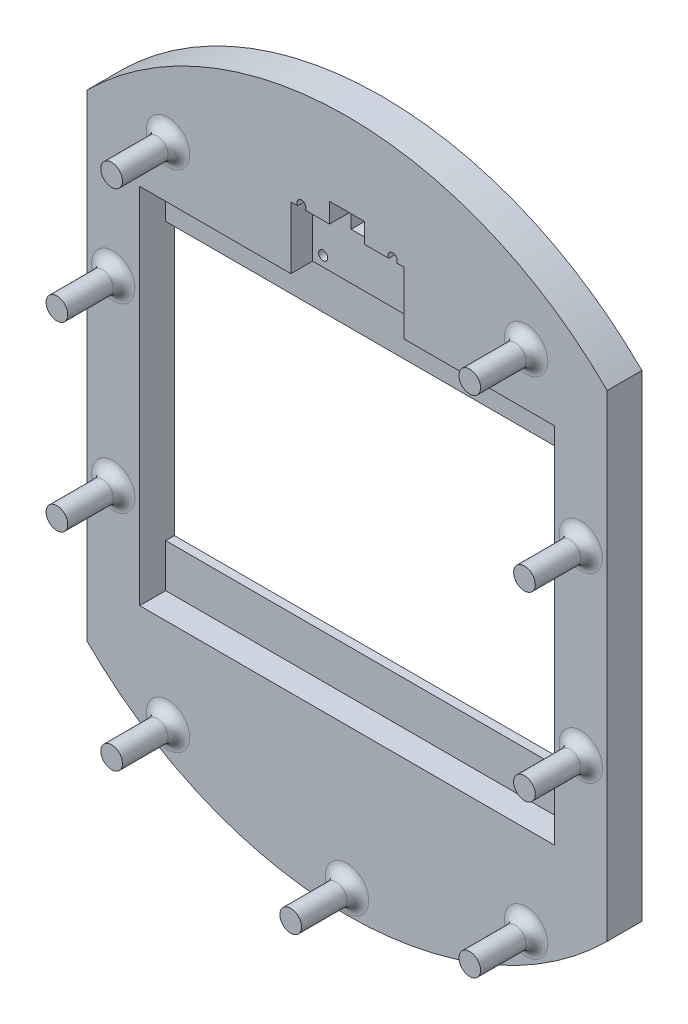
SolidWorks part; units mm, degrees
material "ABS"
ref_plane "Plano frontal" through (0, 0, 0) normal (0, 0, 1) x (1, 0, 0)
ref_plane "Plano superior" through (0, 0, 0) normal (0, 1, 0) x (1, 0, 0)
ref_plane "Plano direito" through (0, 0, 0) normal (1, 0, 0) x (0, 0, -1)
sketch "Esboço1" plane through (0, 0, 0) normal (0, 0, 1) x (1, 0, 0)
  line L0 (0, 0) -> (0, -110)
  line L1 (120, -110) -> (120, 0)
  line L2 (60, -12.6598) -> (60, -97.3402) construction
  line L3 (120, -55) -> (-37.4329, -55) construction
  line L4 (12.1875, -86.875) -> (107.8125, -86.875)
  line L5 (12.1875, -86.875) -> (12.1875, -23.125)
  line L6 (12.1875, -23.125) -> (107.8125, -23.125)
  line L7 (107.8125, -86.875) -> (107.8125, -23.125)
  line L8 (12.1875, -86.875) -> (107.8125, -23.125) construction
  line L9 (12.1875, -23.125) -> (107.8125, -86.875) construction
  arc A4 (0, 0) -> (120, 0) centre (60, -60.208) cw
  arc A5 (0, -110) -> (120, -110) centre (60, -49.792) ccw
  point P9 (60, -55)
  point P16 (0, 0)
  point P17 (60, 24.792)
  point P18 (0, 0)
  point P19 (0, 0)
  dimension "D1" = 110
  dimension "D5" = 85
  dimension "D2" = 63.75
  dimension "D3" = 95.625
extrude "Ressalto-extrusão1" add sketch "Esboço1" along normal blind 8
sketch "Esboço2" plane through (0, 0, 8) normal (0, 0, 1) x (1, 0, 0)
  line L0 (12.1875, -55) -> (107.8125, -55) construction
  line L1 (12.1875, -23.125) -> (12.1875, -86.875) construction
  line L2 (107.8125, -86.875) -> (107.8125, -23.125) construction
  line L3 (107.8125, -23.125) -> (12.1875, -23.125) construction
  line L4 (12.1875, -96.875) -> (107.8125, -96.875)
  line L5 (12.1875, -96.875) -> (12.1875, -13.125)
  line L6 (12.1875, -13.125) -> (107.8125, -13.125)
  line L7 (107.8125, -96.875) -> (107.8125, -13.125)
  line L8 (12.1875, -96.875) -> (107.8125, -13.125) construction
  line L9 (12.1875, -13.125) -> (107.8125, -96.875) construction
  point P6 (60, -55)
  dimension "D1" = 10
extrude "Corte-extrusão1" cut sketch "Esboço2" against normal blind 6
sketch "Esboço3" plane through (0, 0, 8) normal (0, 0, 1) x (1, 0, 0)
  line L0 (-24.8022, -52.3385) -> (153.0643, -52.3385) construction
  line L1 (113.9062, -94.6477) -> (113.9062, -101.6218) construction
  line L3 (60, 24.792) -> (60, -134.792) construction
  line L4 (12.1875, -13.125) -> (0, -13.125) construction
  line L5 (0, 0) -> (0, -110) construction
  line L6 (0, -13.125) -> (6.0938, -13.125) construction
  line L7 (6.0938, -13.125) -> (6.0938, -107.383) construction
  line L8 (35.13, -13.125) -> (35.13, -106.875) construction
  line L9 (107.8125, -13.125) -> (12.1875, -13.125) construction
  line L10 (60, -134.792) -> (60, -106.875)
  arc A0 (6.0938, -107.383) -> (113.9062, -107.383) centre (60, -52.3385) ccw
  circle A1 centre (18.7084, -117.383) radius 2.5
  circle A2 centre (60, -129.3825) radius 2.5
  circle A3 centre (101.2916, -117.383) radius 2.5
  circle A4 centre (101.2916, -1.0648) radius 2.5
  circle A6 centre (18.7084, -1.0648) radius 2.5
  arc A7 (120, 0) -> (0, 0) centre (60, -60.208) ccw construction
  arc A8 (0, -110) -> (120, -110) centre (60, -49.792) ccw construction
  circle A9 centre (6.0938, -75.94) radius 2.5
  circle A10 centre (6.0938, -34.065) radius 2.5
  circle A11 centre (113.9062, -75.94) radius 2.5
  circle A12 centre (113.9062, -34.065) radius 2.5
  point P2 (113.9062, -106.875)
  point P6 (0, 0)
  point P17 (0, 0)
  point P18 (0, 0)
  point P39 (60, -13.125)
  point P48 (18.7084, -1.0648)
  point P51 (101.2916, -1.0648)
  dimension "D1" = 5
  dimension "D2" = 5
  dimension "D7" = 77.044
  dimension "D3" = 41.875
  dimension "D4" = 20.94
  dimension "D5" = 10
  dimension "D6" = 94.258
  dimension "D8" = 41.2916
  dimension "D9" = 27.917
  dimension "D10" = 37.917
  dimension "D11" = 5.4095
  dimension "D12" = 107.8125
extrude "Ressalto-extrusão2" add sketch "Esboço3" along normal blind 13 contours A9 | A1 | A2 | A3 | A11 | A12 | A4 | A6 | A10
fillet "Filete1" radius 2.5 9 edges at (16.2084, -1.0648, 8) (3.5938, -34.065, 8) (3.5937, -75.94, 8) (16.2084, -117.383, 8) (57.5, -129.3825, 8) (98.7916, -117.383, 8) (111.4062, -75.94, 8) (111.4062, -34.065, 8) (98.7916, -1.0648, 8)
sketch "Esboço4" plane through (0, 0, 8) normal (0, 0, 1) x (1, 0, 0)
  line L1 (64.05, -2.3159) -> (55.95, -2.3159)
  line L2 (64.05, -2.3159) -> (64.05, 5.7841)
  line L3 (64.05, 5.7841) -> (55.95, 5.7841)
  line L4 (55.95, -2.3159) -> (55.95, 5.7841)
  line L5 (64.05, -2.3159) -> (55.95, 5.7841) construction
  line L6 (64.05, 5.7841) -> (55.95, -2.3159) construction
  circle A0 centre (70.5, -10.7659) radius 1.05
  circle A1 centre (70.5, 1.7341) radius 1.05
  circle A2 centre (49.5, -10.7659) radius 1.05
  circle A3 centre (49.5, 1.7341) radius 1.05
  point P0 (60, 1.7341)
  dimension "D3" = 2.1
  dimension "D1" = 8.1
  dimension "D2" = 8.1
extrude "Corte-extrusão2" cut sketch "Esboço4" against normal blind 14
sketch "Esboço5" plane through (0, 0, 8) normal (0, 0, 1) x (1, 0, 0)
  line L0 (47.0593, -13.125) -> (47.0593, 1.21)
  line L1 (107.8125, -13.125) -> (12.1875, -13.125) construction
  line L2 (47.0593, 1.21) -> (73.076, 1.21)
  line L3 (73.076, 1.21) -> (73.076, -25.3836)
  line L4 (73.076, -25.3836) -> (47.0593, -25.3836)
  line L5 (47.0593, -25.3836) -> (47.0593, -13.125)
extrude "Corte-extrusão3" cut sketch "Esboço5" against normal blind 5
